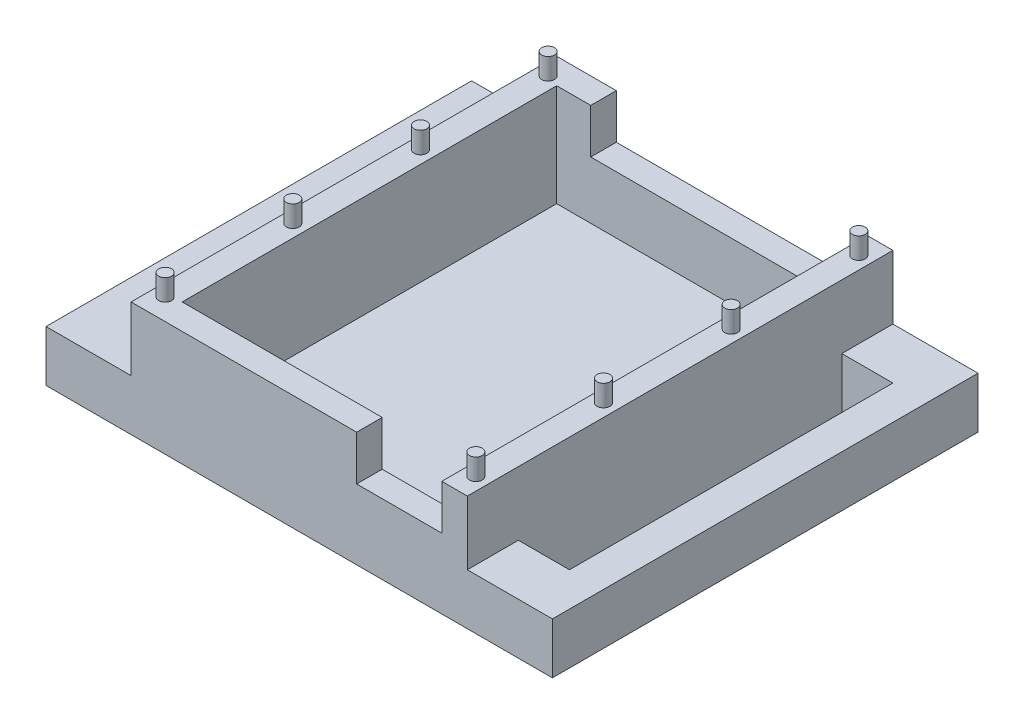
SolidWorks part; units mm, degrees
ref_plane "Front Plane" through (0, 0, 0) normal (0, 0, 1) x (1, 0, 0)
ref_plane "Top Plane" through (0, 0, 0) normal (0, 1, 0) x (1, 0, 0)
ref_plane "Right Plane" through (0, 0, 0) normal (1, 0, 0) x (0, 0, -1)
sketch "Sketch1" plane through (0, 0, 0) normal (0, 1, 0) x (1, 0, 0)
  line L1 (0, 0) -> (39.5, 0)
  line L2 (0, 0) -> (0, 50)
  line L3 (0, 50) -> (39.5, 50)
  line L4 (39.5, 0) -> (39.5, 50)
  dimension "D1" = 39.5
  dimension "D2" = 50
extrude "Boss-Extrude1" add sketch "Sketch1" along normal blind 1.5
sketch "Sketch3" plane through (0, 1.5, 0) normal (0, 1, 0) x (1, 0, 0)
  line L1 (0, 0) -> (39.5, 0)
  line L2 (0, 0) -> (0, 50)
  line L3 (0, 50) -> (39.5, 50)
  line L4 (39.5, 0) -> (39.5, 50)
  line L5 (3, 3) -> (36.5, 3)
  line L6 (3, 3) -> (3, 47)
  line L7 (3, 47) -> (36.5, 47)
  line L8 (36.5, 3) -> (36.5, 47)
  dimension "D1" = 44
  dimension "D2" = 33.5
  dimension "D3" = 3
  dimension "D4" = 3
extrude "Boss-Extrude2" add sketch "Sketch3" along normal blind 12
sketch "Sketch6" plane through (0, 0, 0) normal (0, 0, 1) x (1, 0, 0)
  line L0 (39.5, 13.5) -> (39.5, 0) construction
  line L1 (26.5, 14.23) -> (36.5, 14.23)
  line L2 (26.5, 14.23) -> (26.5, 8.23)
  line L3 (26.5, 8.23) -> (36.5, 8.23)
  line L4 (36.5, 14.23) -> (36.5, 8.23)
  line L5 (0, 0) -> (39.5, 0) construction
  point P4 (39.5, 6.75)
  dimension "D1" = 10
  dimension "D2" = 6
  dimension "D3" = 3
  dimension "D4" = 8.23
extrude "Cut-Extrude2" cut sketch "Sketch6" against normal blind 11.2
sketch "Sketch7" plane through (0, 0, -50) normal (0, 0, -1) x (-1, 0, 0)
  line L0 (-39.5, 13.5) -> (-39.5, 0) construction
  line L1 (-36.5, 14.23) -> (-7, 14.23)
  line L2 (-36.5, 14.23) -> (-36.5, 8.25)
  line L3 (-36.5, 8.25) -> (-7, 8.25)
  line L4 (-7, 14.23) -> (-7, 8.25)
  line L5 (-39.5, 0) -> (0, 0) construction
  dimension "D1" = 29.5
  dimension "D2" = 5.98
  dimension "D3" = 3
  dimension "D4" = 8.25
extrude "Cut-Extrude3" cut sketch "Sketch7" against normal blind 3.3
sketch "Sketch8" plane through (39.5, 0, 0) normal (1, 0, 0) x (0, 0, -1)
  line L1 (0, 0) -> (6, 0)
  line L2 (0, 0) -> (0, 6)
  line L3 (0, 6) -> (6, 6)
  line L4 (6, 0) -> (6, 6)
  line L5 (50, 0) -> (44, 0)
  line L6 (50, 0) -> (50, 6)
  line L7 (50, 6) -> (44, 6)
  line L8 (44, 0) -> (44, 6)
  dimension "D1" = 6
  dimension "D2" = 6
  dimension "D3" = 6
  dimension "D4" = 6
extrude "Boss-Extrude3" add sketch "Sketch8" along normal blind 10
sketch "Sketch9" plane through (0, 0, -44) normal (0, 0, 1) x (1, 0, 0)
  line L0 (49.5, 0) -> (39.5, 0) construction
  line L1 (49.5, 6) -> (45.5, 6)
  line L2 (49.5, 6) -> (49.5, 0)
  line L3 (49.5, 0) -> (45.5, 0)
  line L4 (45.5, 6) -> (45.5, 0)
  dimension "D1" = 4
extrude "Boss-Extrude4" add sketch "Sketch9" along normal blind 38
sketch "Sketch10" plane through (0, 0, 0) normal (-1, 0, 0) x (0, 0, 1)
  line L1 (-50, 0) -> (-44, 0)
  line L2 (-50, 0) -> (-50, 6)
  line L3 (-50, 6) -> (-44, 6)
  line L4 (-44, 0) -> (-44, 6)
  line L5 (0, 0) -> (-6, 0)
  line L6 (0, 0) -> (0, 6)
  line L7 (0, 6) -> (-6, 6)
  line L8 (-6, 0) -> (-6, 6)
  dimension "D1" = 6
  dimension "D2" = 6
  dimension "D3" = 6
  dimension "D4" = 6
extrude "Boss-Extrude5" add sketch "Sketch10" along normal blind 10
sketch "Sketch11" plane through (0, 0, -6) normal (0, 0, -1) x (-1, 0, 0)
  line L0 (10, 6) -> (0, 6) construction
  line L1 (10, 0) -> (6, 0)
  line L2 (10, 0) -> (10, 6)
  line L3 (10, 6) -> (6, 6)
  line L4 (6, 0) -> (6, 6)
  dimension "D1" = 4
extrude "Boss-Extrude6" add sketch "Sketch11" along normal blind 38
sketch "Sketch12" plane through (0, 13.5, 0) normal (0, 1, 0) x (1, 0, 0)
  line L0 (36.5, 0) -> (39.5, 0) construction
  line L2 (36.5, 0) -> (36.5, 50) construction
  line L3 (0, 0) -> (26.5, 0) construction
  line L4 (0, 50) -> (0, 0) construction
  circle A0 centre (38, 2.5) radius 0.75
  circle A1 centre (1.5, 2.5) radius 0.75
  dimension "D1" = 1.5
  dimension "D4" = 1.5
  dimension "D2" = 2.5
  dimension "D3" = 1.5
  dimension "D5" = 2.5
  dimension "D6" = 1.5
extrude "Boss-Extrude7" add sketch "Sketch12" along normal blind 2.5
pattern_linear "LPattern1" count 4 spacing 15 along (0, 0, -1) of "Boss-Extrude7"
